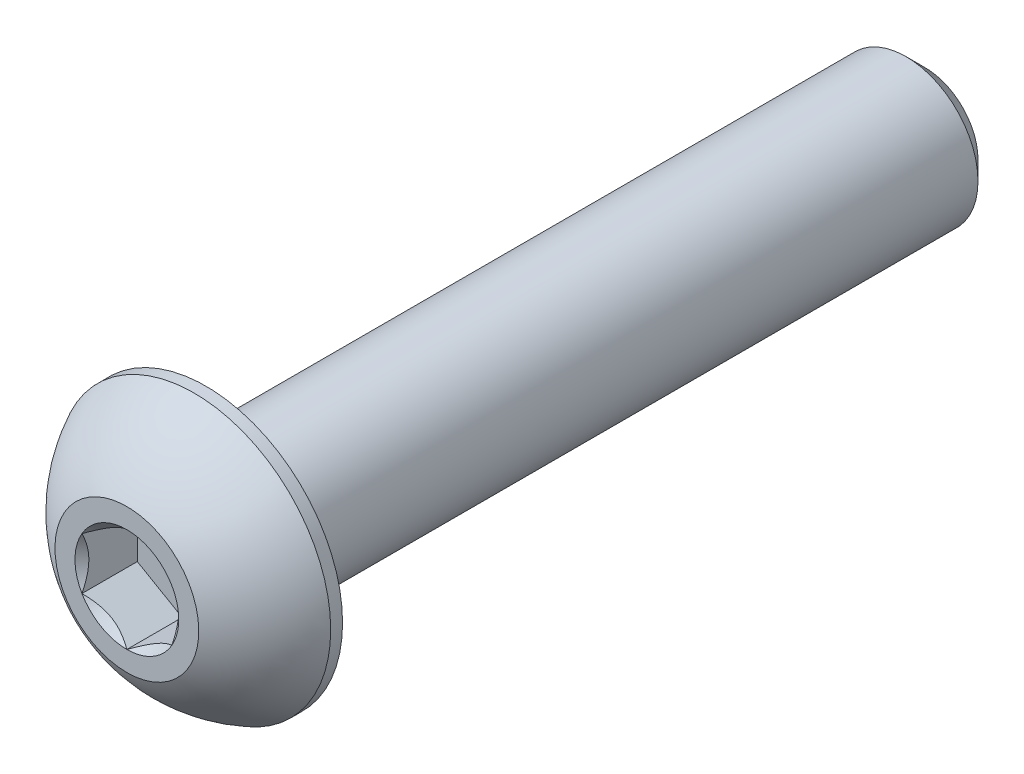
SolidWorks part; units mm, degrees
ref_plane "Front" through (0, 0, 0) normal (0, 0, 1) x (1, 0, 0)
ref_plane "Top" through (0, 0, 0) normal (0, 1, 0) x (1, 0, 0)
ref_plane "Right" through (0, 0, 0) normal (1, 0, 0) x (0, 0, -1)
sketch "Sketch1" plane through (0, 0, 0) normal (1, 0, 0) x (0, 0, -1)
  line L2 (2.2, 2) -> (22.2, 2)
  line L3 (22.2, 2) -> (22.2, 0)
  line L4 (22.2, 0) -> (2.2, 0)
  line L6 (1.87, 3.8) -> (2.2, 3.8) construction
  line L7 (22.2, 2) -> (22.2, -2) construction
  line L8 (0, 0) -> (2.2, 0) construction
  line L9 (2.2, 3.8) -> (2.2, -3.8) construction
  line L11 (2.2, 2) -> (2.2, 0)
  line L13 (0, 1.25) -> (0, -1.25) construction
  line L14 (0, 1.25) -> (0, 2) construction
  line L15 (22.1562, 2.0758) -> (22.5062, 1.4696) construction
  line L16 (22.5062, 1.4696) -> (22.8562, 2.0758) construction
  line L17 (22.8562, 2.0758) -> (22.1562, 2.0758) construction
  line L18 (22.2, 2) -> (22.8125, 2) construction
  line L19 (22.5062, 2.0758) -> (22.5062, 2) construction
  line L20 (22.5062, 2) -> (22.5062, 1.5453) construction
  line L21 (22.5062, 1.5453) -> (22.5062, 1.4696) construction
  line L22 (22.4625, 1.5453) -> (22.55, 1.5453)
  line L23 (22.1781, 2.0379) -> (22.8344, 2.0379)
  line L24 (22.55, 1.5453) -> (22.8344, 2.0379)
  line L25 (22.4625, 1.5453) -> (22.1781, 2.0379)
  line L26 (21.675, 2) -> (22.2, 1.475)
  arc A3 (0, 2) -> (1.87, 3.8) centre (3.7264, 0) cw construction
  point P29 (22.5062, 2.0379)
  point P30 (20.45, -2)
  dimension "D1" = 0.33
  dimension "Pitch" = 0.7
  dimension "D3" = 0.0875
  dimension "D2" = 0.525
  dimension "D4" = 45
  dimension "D5" = 1.75
sketch "Sketch10" plane through (0, 0, 0) normal (1, 0, 0) x (0, 0, -1)
  line L0 (21.675, 2) -> (22.2, 1.475) construction
  line L1 (21.675, 2) -> (22.2, 1.475)
  line L4 (22.2, 2) -> (2.2, 2)
  line L5 (22.2, 0) -> (22.2, 2)
  line L6 (2.2, 0) -> (22.2, 0)
  line L7 (2.2, 2) -> (2.2, 0)
  line L8 (21.675, 2) -> (2.2, 2)
  line L9 (22.2, 0) -> (22.2, 1.475)
  line L10 (2.2, 0) -> (22.2, 0)
  line L11 (2.2, 2) -> (2.2, 0)
  dimension "D1" = 0
revolve "Revolve3" add sketch "Sketch10" angle 360 about L8
sketch "Sketch7" plane through (0, 0, 0) normal (1, 0, 0) x (0, 0, -1)
  line L6 (1.87, 3.8) -> (2.2, 3.8) construction
  line L8 (0, 0) -> (2.2, 0) construction
  line L11 (2.2, 3.8) -> (2.2, -3.8) construction
  line L12 (1.87, 3.8) -> (2.2, 3.8)
  line L13 (0, 0) -> (2.2, 0)
  line L14 (0, 1.25) -> (0, -1.25) construction
  line L15 (2.2, 3.8) -> (2.2, 0)
  line L16 (0, 2) -> (0, 0)
  arc A2 (1.87, 3.8) -> (0, 2) centre (3.7264, 0) ccw construction
  arc A3 (1.87, 3.8) -> (0, 2) centre (3.7264, 0) ccw
revolve "Revolve2" add sketch "Sketch7" angle 360 mid plane about L13
sketch "Sketch5" plane through (0, 0, 0) normal (0, 0, 1) x (1, 0, 0)
  line L1 (1.25, -0.7217) -> (1.25, 0.7217)
  line L2 (1.25, 0.7217) -> (0, 1.4434)
  line L3 (0, 1.4434) -> (-1.25, 0.7217)
  line L4 (-1.25, 0.7217) -> (-1.25, -0.7217)
  line L5 (-1.25, -0.7217) -> (0, -1.4434)
  line L6 (0, -1.4434) -> (1.25, -0.7217)
  circle A0 centre (0, 0) radius 1.25 construction
extrude "Cut-Extrude2" cut sketch "Sketch5" against normal blind 1.54
sketch "Sketch6" plane through (0, 0, 0) normal (0, 0, 1) x (1, 0, 0)
  circle A0 centre (0, 0) radius 1.4434
extrude "Cut-Extrude3" cut sketch "Sketch6" against normal blind 1.54 draft 45
sketch "Sketch9" [suppressed] plane through (0, 0, -2.2) normal (0, 0, -1) x (-1, 0, 0)
  circle A0 centre (0, 0) radius 2 construction
  circle A4 centre (0, 0) radius 2
split "Split1" [suppressed] bodies to split 113
sketch "Sketch11" [suppressed] plane through (0, 0, -22.2) normal (0, 0, -1) x (-1, 0, 0)
  circle A0 centre (0, 0) radius 2 construction
  circle A1 centre (0, 0) radius 2
curve "Helix/Spiral1" [suppressed] pitch 0.7 height 22.2 turns 31.7143
sketch "Sketch12" [suppressed] plane through (0, 0, 0) normal (1, 0, 0) x (0, 0, -1)
  line L0 (22.4625, 1.5453) -> (22.55, 1.5453) construction
  line L1 (22.55, 1.5453) -> (22.8344, 2.0379) construction
  line L2 (22.1781, 2.0379) -> (22.8344, 2.0379) construction
  line L3 (22.4625, 1.5453) -> (22.1781, 2.0379) construction
  line L4 (22.4625, 1.5453) -> (22.55, 1.5453)
  line L5 (22.55, 1.5453) -> (22.8344, 2.0379)
  line L6 (22.1781, 2.0379) -> (22.8344, 2.0379)
  line L7 (22.4625, 1.5453) -> (22.1781, 2.0379)
sweep "Cut-Sweep2" [suppressed] cut profiles "Sketch12" path "Helix/Spiral1"
extrude "Boss-Extrude1" [suppressed] add sketch "Sketch9" along normal blind 10 draft 45
equation "\"D1@Cut-Extrude2\" = \"Head Ht@Sketch1\" * .7"
equation "\"D1@Sketch1\" = \"Head Ht@Sketch1\" * .15"
equation "\"D1@Cut-Extrude3\" = \"D1@Cut-Extrude2\""
equation "\"D3@Sketch1\" = \"Pitch@Sketch1\" / 8"
equation "\"D2@Sketch1\"=\"Pitch@Sketch1\"*0.75"
equation "\"D3@Helix/Spiral1\" = \"Lg@Sketch1\" + \"Head Ht@Sketch1\""
equation "\"D4@Helix/Spiral1\"=\"pitch@sketch1\""
equation "\"D5@Sketch1\"=\"Pitch@Sketch1\"*2.5"
